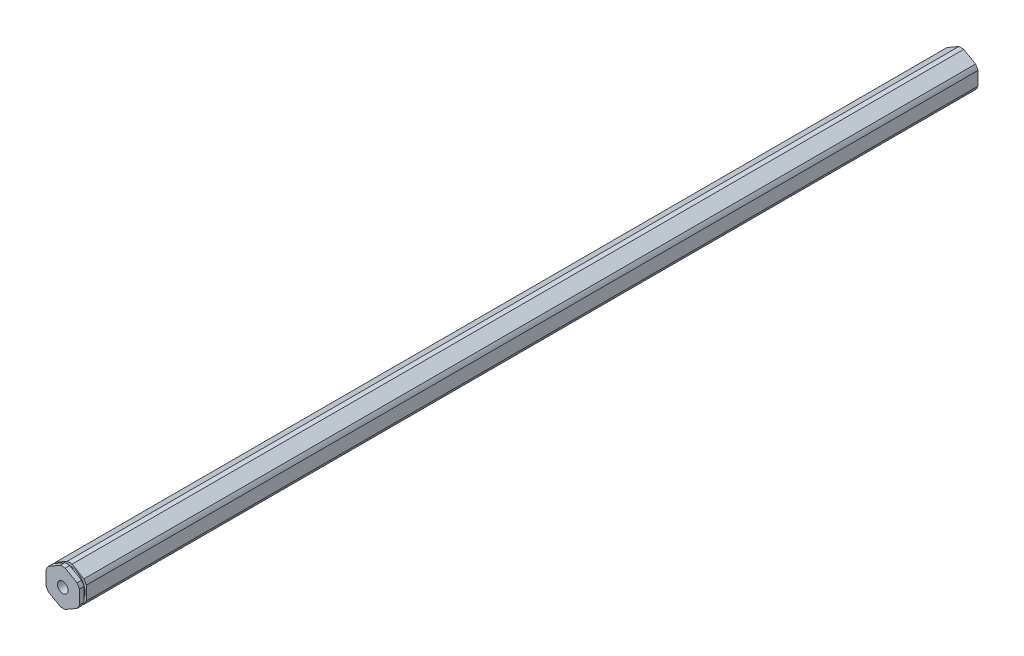
SolidWorks part; units mm, degrees
ref_plane "Front Plane" through (0, 0, 0) normal (0, 0, 1) x (1, 0, 0)
ref_plane "Top Plane" through (0, 0, 0) normal (0, 1, 0) x (1, 0, 0)
ref_plane "Right Plane" through (0, 0, 0) normal (1, 0, 0) x (0, 0, -1)
sketch "Sketch1" plane through (0, 0, 0) normal (0, 0, 1) x (1, 0, 0)
  line L1 (0, 7.3323) -> (-6.35, 3.6662)
  line L2 (-6.35, 3.6662) -> (-6.35, -3.6662)
  line L3 (-6.35, -3.6662) -> (0, -7.3323)
  line L4 (0, -7.3323) -> (6.35, -3.6662)
  line L5 (6.35, -3.6662) -> (6.35, 3.6662)
  line L6 (6.35, 3.6662) -> (0, 7.3323)
  circle A0 centre (0, 0) radius 6.35 construction
  circle A1 centre (0, 0) radius 6.858
  dimension "D1" = 12.7
  dimension "D2" = 13.716
extrude "Boss-Extrude1" add sketch "Sketch1" along normal mid plane 340.741 contours L5 A1 L6 L1 L2 L3 L4 region at (0, 0, 0)
hole_wizard "#10-32 Tapped Hole1" positions "3DSketch1" profile "Sketch2" tap size "#10-32" standard "ANSI Inch"
sketch3d "3DSketch1"
  line L0 (0, 0, 170.3705) -> (0, 0, -170.3705) construction
  line L1 (0, 0, 170.3705) -> (0, 0, -170.3705) construction
  point P0 (0, 0, 170.3705)
  point P4 (0, 0, -170.3705)
sketch "Sketch2" plane through (0, 0, 170.3705) normal (1, 0, 0) x (0, -1, 0)
  line L0 (0, 0) -> (0, 17.5608)
  line L1 (0, 17.5608) -> (2.0193, 16.3474)
  line L2 (2.0193, 16.3474) -> (2.0193, 0)
  line L5 (2.0193, 0) -> (0, 0)
  line L10 (0, 17.5608) -> (-2.0193, 16.3474) construction
  line L11 (0, -6.35) -> (0, 107.95) construction
  dimension "Tap Drill Dia." = 4.0386
  dimension "Tap Drill Depth" = 16.3474
  dimension "Drill Angle" = 118
cosmetic thread "Hole Thread1" parameters "D1"=13.97, "D2"=4.826
cosmetic thread "Hole Thread2" parameters "D1"=13.97, "D2"=4.826
sketch "Sketch5" plane through (0, 0, 0) normal (1, 0, 0) x (0, 0, -1)
  line L0 (170.3705, 6.858) -> (-170.3705, 6.858) construction
  line L1 (-168.656, 6.858) -> (-167.767, 6.858)
  line L2 (-168.656, 6.858) -> (-168.656, 5.8547)
  line L3 (-168.656, 5.8547) -> (-167.767, 5.8547)
  line L4 (-167.767, 6.858) -> (-167.767, 5.8547)
  line L5 (-165.0472, 0) -> (-158.8423, 0) construction
  dimension "D1" = 5.8547
  dimension "D2" = 0.889
  dimension "D3" = 1.7145
revolve "Cut-Revolve1" cut sketch "Sketch5" angle 360 about L5
mirror "Mirror1" [suppressed] about plane through (0, 0, 0) normal (0, 0, 1)
